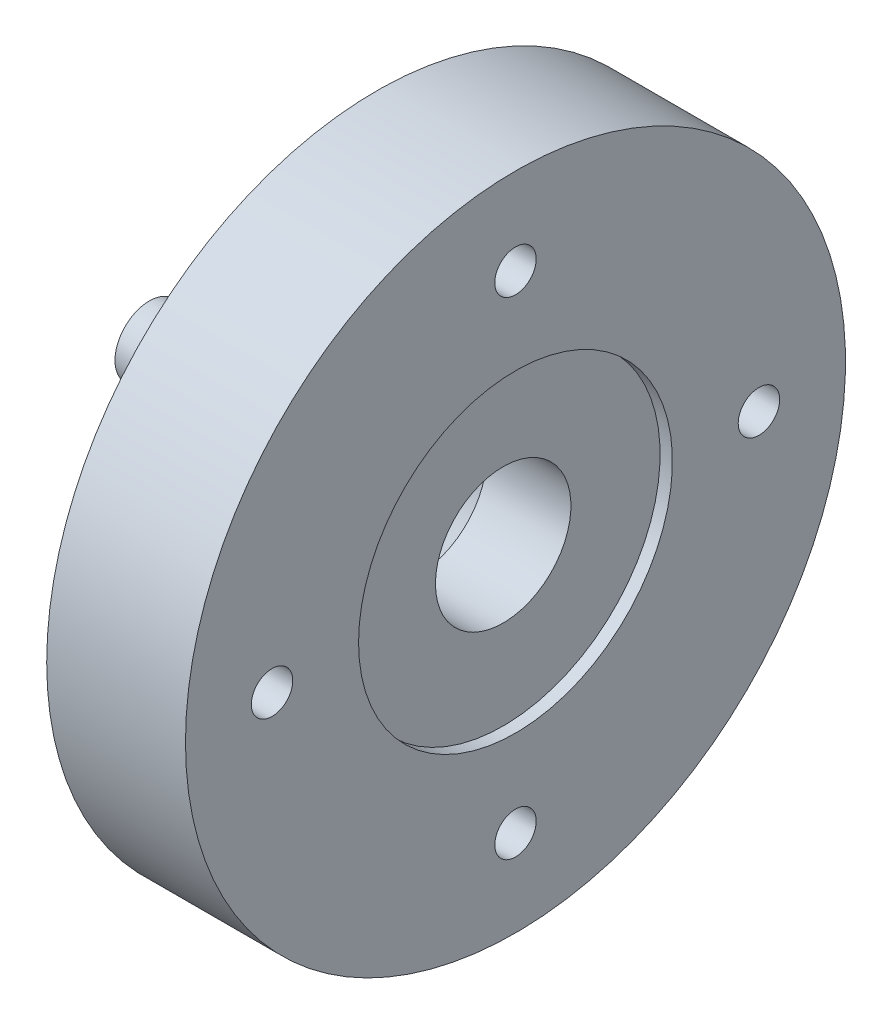
SolidWorks part; units mm, degrees
ref_plane "Front Plane" through (0, 0, 0) normal (0, 0, 1) x (1, 0, 0)
ref_plane "Top Plane" through (0, 0, 0) normal (0, 1, 0) x (1, 0, 0)
ref_plane "Right Plane" through (0, 0, 0) normal (1, 0, 0) x (0, 0, -1)
sketch "Sketch1" plane through (0, 0, 0) normal (0, 0, 1) x (1, 0, 0)
  line L0 (-795.1638, 11.7142) -> (36114.285, 11.7142) construction
  line L3 (-71.2919, 14.8842) -> (-71.2919, 14.5342)
  line L8 (-75.7419, 13.3992) -> (-59.4889, 13.3992)
  line L9 (-75.7419, 13.3992) -> (-75.7419, 14.5342)
  line L10 (-45.7058, 24.5892) -> (-45.7058, 38.788)
  line L12 (-45.7058, 38.788) -> (-57.0912, 38.788)
  line L13 (-62.3716, 14.5342) -> (-59.4889, 23.788)
  line L16 (-45.7058, 24.5892) -> (-46.7158, 24.5892)
  line L17 (-46.7158, 24.5892) -> (-46.7158, 17.2704)
  line L18 (-57.0912, 38.788) -> (-57.0912, 23.788)
  line L19 (-59.4889, 23.788) -> (-57.0912, 23.788)
  line L20 (-59.4889, 13.3992) -> (-53.6375, 17.2704)
  line L21 (-75.7419, 14.5342) -> (-71.2919, 14.8842)
  line L22 (-53.6375, 17.2704) -> (-46.7158, 17.2704)
  line L23 (-71.2919, 14.5342) -> (-66.8419, 14.8842)
  line L24 (-44.6958, 24.5892) -> (-45.7058, 24.5892) construction
  line L25 (-37.7741, 17.2704) -> (-44.6958, 17.2704) construction
  line L26 (-66.8419, 14.8842) -> (-66.8419, 14.5342)
  line L27 (-66.8419, 14.5342) -> (-62.3716, 14.8842)
  line L28 (-62.3716, 14.8842) -> (-62.3716, 14.5342)
  point P23 (0, 0)
  point P24 (-44.658, 25.4232)
  point P25 (0, 0)
  dimension "D2" = 6.34
  dimension "D3" = 1.01
  dimension "D4" = 15
  dimension "D6" = 3.37
  dimension "D7" = 5.64
revolve "Revolve17" add sketch "Sketch1" angle 360 about L0
sketch "Sketch3" plane through (-57.0912, 0, 0) normal (-1, 0, 0) x (0, 0, 1)
  circle A2 centre (0, 11.7142) radius 19.9711 construction
  point P2 (0, 31.6853)
  point P3 (19.9711, 11.7142)
  point P4 (0, -8.2569)
  point P6 (-19.9711, 11.7142)
hole_wizard "CBORE for M3 Hex Socket Head Cap Screw1" positions "Sketch3" profile "Sketch4" counterbore size "M3" standard "ISO" end condition through all
sketch "Sketch4" plane through (-57.0912, 11.7142, -19.9711) normal (0, 1, 0) x (0, 0, 1)
  line L0 (0, 0) -> (0, 11.3854)
  line L1 (0, 11.3854) -> (1.7, 11.3854)
  line L3 (1.7, 11.3854) -> (1.7, 3.4)
  line L4 (1.675, 3.4) -> (1.7, 3.4)
  line L5 (1.675, 3.4) -> (1.675, 0.025)
  line L6 (1.675, 0.025) -> (1.7, 0)
  line L7 (1.7, 0) -> (0, 0)
  line L8 (-1.675, 0.025) -> (-1.7, 0) construction
  line L11 (0, -6.35) -> (0, 107.95) construction
  dimension "Thru Hole Dia." = 3.4
  dimension "Thru Hole Depth" = 11.3854
  dimension "Near C'Sink Angle" = 90
